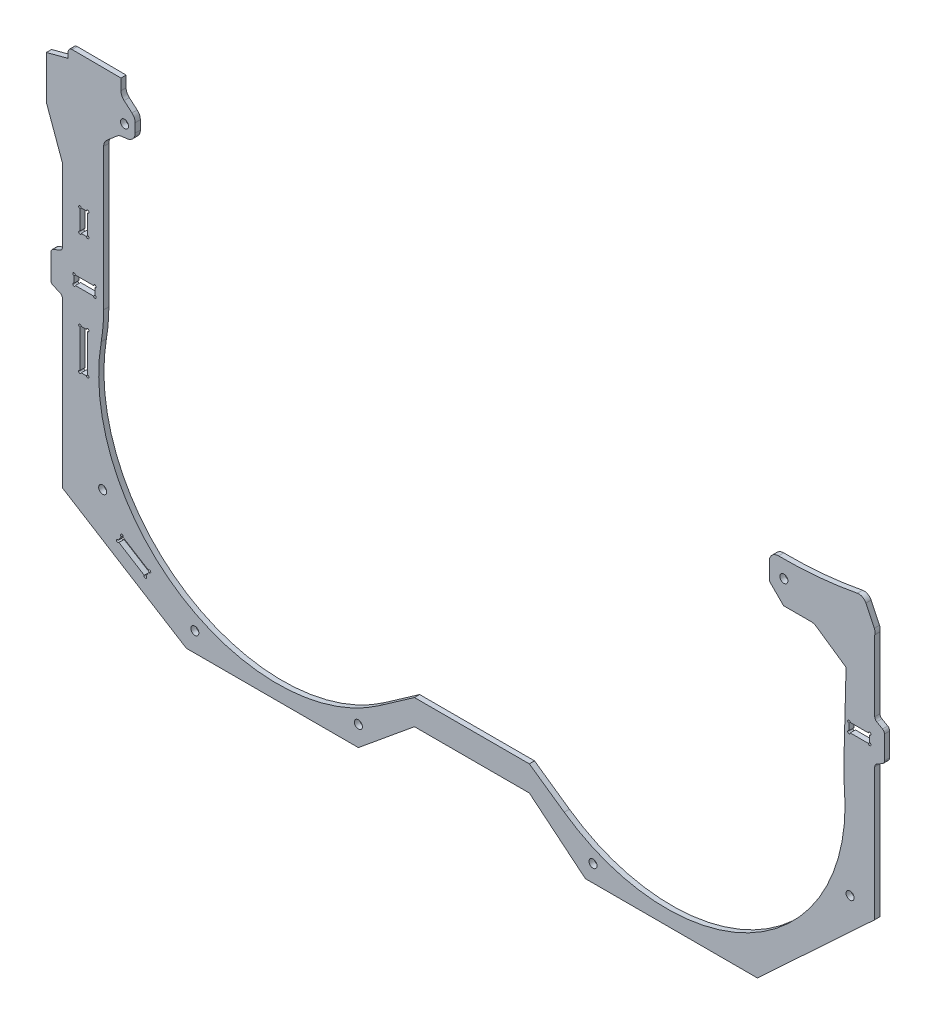
SolidWorks part; units mm, degrees
material "PPS"
ref_plane "前视基准面" through (0, 0, 0) normal (0, 0, 1) x (1, 0, 0)
ref_plane "上视基准面" through (0, 0, 0) normal (0, 1, 0) x (1, 0, 0)
ref_plane "右视基准面" through (0, 0, 0) normal (1, 0, 0) x (0, 0, -1)
sketch "草图1" plane through (0, 0, 0) normal (0, 0, 1) x (1, 0, 0)
  line L0 (-816.4831, 0) -> (39952.7477, 0) construction
  line L1 (0, 10.8762) -> (0, -592.6628) construction
  line L2 (0, 0) -> (206.9686, -284.8678) construction
  line L9 (155.1848, -135.6229) -> (109.9887, -177.6457)
  line L10 (109.9887, -177.6457) -> (43.7257, -177.6457)
  line L60 (-109.9887, -177.6457) -> (-43.7257, -177.6457)
  line L119 (-135.8935, -19.3983) -> (-141.8504, -24.5203)
  line L187 (152.75, -77.5) -> (145.75, -77.5) construction
  line L188 (152.75, -77.5) -> (152.75, -75) construction
  line L189 (145.75, -77.5) -> (145.75, -75) construction
  line L190 (152.75, -75) -> (145.75, -75) construction
  line L191 (-145.75, -75) -> (-152.75, -75) construction
  line L192 (-152.75, -75) -> (-152.75, -77.5) construction
  line L193 (-152.75, -77.5) -> (-145.75, -77.5) construction
  line L194 (-145.75, -77.5) -> (-145.75, -75) construction
  line L195 (145.25, -74.5) -> (153.25, -74.5)
  line L196 (153.25, -74.5) -> (153.25, -78)
  line L197 (153.25, -78) -> (145.25, -78)
  line L198 (145.25, -78) -> (145.25, -74.5)
  line L199 (-153.25, -78) -> (-145.25, -78)
  line L200 (-153.25, -74.5) -> (-153.25, -78)
  line L201 (-145.25, -74.5) -> (-153.25, -74.5)
  line L202 (-145.25, -78) -> (-145.25, -74.5)
  line L204 (-135.1929, 0) -> (-155.5041, 0.108)
  line L205 (-155.5041, 3.8169) -> (-155.5041, -3.6009) construction
  line L206 (-155.5041, 0.108) -> (-155.5041, -3.6009)
  line L207 (-155.5041, -3.6009) -> (-163.9299, -5.8429)
  line L208 (-155.5041, -3.6009) -> (-170.0041, -7.4592) construction
  line L209 (-163.9299, -5.8429) -> (-163.9299, -22.4613)
  line L210 (-163.9299, -22.4613) -> (-157.7253, -39.5836)
  line L211 (-157.7253, -39.5836) -> (-157.7253, -148.0115)
  line L212 (-157.7253, -148.0115) -> (-109.9887, -177.6457)
  line L215 (114.5778, -32.685) -> (114.5778, -42.9165)
  line L216 (120.0778, -48.4165) -> (131.782, -48.4165)
  line L217 (131.782, -48.4165) -> (144.1391, -56.9362)
  line L219 (151.7709, -31.6811) -> (155.0114, -38.4796)
  line L220 (155.1848, -40.6053) -> (155.1848, -135.6229)
  line L221 (120.1823, -39.335) -> (149.4323, -39.335) construction
  line L222 (91.0014, -48.4165) -> (142.5788, -48.4165) construction
  line L223 (75, -103.2286) -> (164.6276, -103.2286) construction
  line L224 (75, -103.2286) -> (35.5666, -159.5453) construction
  line L226 (35.5666, -159.5453) -> (22.126, -150.1341)
  line L227 (22.126, -150.1341) -> (-22.126, -150.1341)
  line L228 (22.126, -159.8702) -> (-22.126, -159.8702)
  line L229 (22.126, -159.8702) -> (43.7257, -177.6457)
  line L230 (-35.5666, -159.5453) -> (-22.126, -150.1341)
  line L231 (-22.126, -159.8702) -> (-43.7257, -177.6457)
  line L233 (114.5778, -42.9165) -> (120.0778, -48.4165)
  line L234 (75, -103.2286) -> (143.1618, -94.255) construction
  line L235 (144.1391, -56.9362) -> (143.1618, -94.255)
  line L236 (143.1618, -94.255) -> (143.1618, -60.7022) construction
  line L238 (-141.8504, -87.1793) -> (-75, -103.2286) construction
  line L239 (-75, -103.2286) -> (-143.75, -103.2286) construction
  line L240 (-141.8504, -24.5203) -> (-141.8504, -87.1793)
  line L241 (-135.1929, 0) -> (-135.1929, -5.85)
  line L242 (-135.1929, -5.85) -> (-129.7197, -10.5767)
  line L243 (-129.7197, -10.5767) -> (-129.7197, -18.7984)
  line L244 (-129.7197, -18.7984) -> (-135.8935, -19.3983)
  circle A76 centre (75, -103.2286) radius 68.75 construction
  circle A78 centre (-133.8062, -14.6009) radius 1.55
  arc A79 (155.0114, -38.4796) -> (155.1848, -40.6053) centre (152.3033, -39.7704) cw
  circle A80 centre (-75, -103.2286) radius 68.75 construction
  arc A81 (148.5011, -30.0249) -> (151.7709, -31.6811) centre (149.0628, -32.9719) cw
  arc A82 (153.902, -42.309) -> (155.0114, -38.4796) centre (152.3033, -39.7704) ccw construction
  arc A83 (148.5011, -30.0249) -> (114.5778, -32.685) centre (119.5082, 122.0773) cw
  arc A84 (97.7907, -31.2329) -> (148.5011, -30.0249) centre (119.5082, 122.0773) ccw construction
  circle A85 centre (149.4323, -39.335) radius 1.55 construction
  circle A86 centre (120.1823, -39.335) radius 1.55
  arc A87 (35.5666, -159.5453) -> (143.75, -103.2286) centre (75, -103.2286) ccw
  arc A88 (-35.5666, -159.5453) -> (-143.75, -103.2286) centre (-75, -103.2286) cw
  arc A89 (143.1618, -94.255) -> (143.75, -103.2286) centre (75, -103.2286) cw
  arc A91 (-143.75, -103.2286) -> (-141.8504, -87.1793) centre (-75, -103.2286) cw
  point P10 (149.25, -75)
  point P29 (0, -150.1341)
  point P32 (110.8616, -177.1038)
  point P38 (153.25, -76.25)
  point P92 (0, -159.8702)
  dimension "D1" = 36
  dimension "D2" = 75
  dimension "D3" = 137.5
  dimension "D6" = 75
  dimension "D7" = 149.25
  dimension "D15" = 125
  dimension "D14" = 3.1
  dimension "D4" = 2.5
  dimension "D5" = 7
  dimension "D8" = 7
  dimension "D9" = 0.5
  dimension "D10" = 0.5
  dimension "D11" = 0.5
  dimension "D12" = 0.5
  dimension "D13" = 29.25
  dimension "D16" = 7.5
  dimension "D17" = 1.5
  dimension "D18" = 13.5
extrude "凸台-拉伸1" add sketch "草图1" along normal blind 2
sketch "草图2" plane through (0, 0, 0) normal (0, 0, 1) x (1, 0, 0)
  line L0 (155.1848, -68.75) -> (158.9348, -70.9151)
  line L1 (155.1848, -135.6229) -> (155.1848, -40.6053) construction
  line L2 (158.9348, -70.9151) -> (158.9348, -81.5849)
  line L3 (158.9348, -81.5849) -> (155.1848, -83.75)
  line L4 (155.1848, -83.75) -> (155.1848, -68.75)
  line L5 (153.25, -76.25) -> (184.2947, -76.25) construction
  line L6 (153.25, -78) -> (153.25, -74.5) construction
  line L7 (-153.25, -76.25) -> (-171.2105, -76.25) construction
  line L8 (-153.25, -74.5) -> (-153.25, -78) construction
  line L9 (-157.7253, -68.75) -> (-157.7253, -83.75)
  line L10 (-157.7253, -39.5836) -> (-157.7253, -148.0115) construction
  line L11 (-157.7253, -83.75) -> (-162.2253, -81.886)
  line L12 (-162.2253, -81.886) -> (-162.2253, -70.614)
  line L13 (-162.2253, -70.614) -> (-157.7253, -68.75)
  dimension "D1" = 3.75
  dimension "D2" = 7.5
  dimension "D3" = 60
  dimension "D4" = 67.5
  dimension "D5" = 4.5
extrude "凸台-拉伸2" add sketch "草图2" against normal up to surface from surface up to face at (-132.2562, -14.6009, 0) starting at face at (149.25, -76.25, 2)
fillet "圆角1" radius 66.25 2 edges at (-141.8504, -87.1793, 1) (143.1618, -94.255, 1)
fillet "圆角4" radius 1.5 9 edges at (155.1848, -68.75, 1) (158.9348, -70.9151, 1) (155.1848, -83.75, 1) (158.9348, -81.5849, 1) (-155.5041, 0.108, 1) (-157.7253, -68.75, 1) (-162.2253, -70.614, 1) (-162.2253, -81.886, 1) (-157.7253, -83.75, 1)
sketch "板状设备接口" plane through (0, 0, 2) normal (0, 0, 1) x (1, 0, 0)
  line L0 (-151, -90.5) -> (-148, -90.5)
  line L1 (-148, -90.5) -> (-148, -106)
  line L2 (-148, -106) -> (-151, -106)
  line L3 (-151, -106) -> (-151, -90.5)
  line L4 (-148, -77.5) -> (-148, -75) construction
  line L5 (-151, -75) -> (-151, -77.5) construction
  line L6 (-151, -51) -> (-148, -51)
  line L7 (-148, -51) -> (-148, -59.5)
  line L8 (-148, -59.5) -> (-151, -59.5)
  line L9 (-151, -59.5) -> (-151, -51)
  line L10 (-145.25, -74.5) -> (-153.25, -74.5) construction
  line L11 (-153.25, -78) -> (-145.25, -78) construction
  line L12 (-134.8158, -152.523) -> (-124.1957, -159.1157)
  line L13 (-124.1957, -159.1157) -> (-125.778, -161.6645)
  line L14 (-125.778, -161.6645) -> (-136.398, -155.0718)
  line L15 (-136.398, -155.0718) -> (-134.8158, -152.523)
  line L21 (-157.7253, -148.0115) -> (-109.9887, -177.6457) construction
  line L22 (-131.088, -158.3682) -> (-133.857, -162.8286) construction
  dimension "D1" = 15
  dimension "D2" = 8.5
  dimension "D3" = 12.5
  dimension "D4" = 15.5
  dimension "D5" = 5.25
  dimension "D6" = 12.5
  dimension "D7" = 3
extrude "设备接口" cut sketch "板状设备接口" against normal through all
sketch "草图4" plane through (0, 0, 0) normal (0, 0, 1) x (1, 0, 0)
  line L0 (-157.7253, -84.7523) -> (-157.7253, -148.0115) construction
  line L1 (-109.9887, -177.6457) -> (-43.7257, -177.6457) construction
  line L2 (155.1848, -135.6229) -> (155.1848, -84.616) construction
  line L3 (-43.7257, -169.8957) -> (-43.7257, -177.6457) construction
  line L4 (43.7257, -177.6457) -> (109.9887, -177.6457) construction
  circle A0 centre (-142.2253, -140.8215) radius 1.55
  circle A1 centre (-43.7257, -169.8957) radius 1.55
  circle A2 centre (-106.713, -170.1457) radius 1.55
  circle A3 centre (46.656, -171.1457) radius 1.55
  circle A4 centre (145.6848, -132.301) radius 1.55
  dimension "D5" = 3.1
  dimension "D1" = 15.5
  dimension "D2" = 7.5
  dimension "D3" = 7.75
  dimension "D4" = 9.5
  dimension "D6" = 6.5
extrude "切除-拉伸3" cut sketch "草图4" along normal through all
fillet "圆角5" radius 3.5 7 edges at (131.782, -48.4165, 1) (114.5778, -32.685, 1) (-141.8504, -24.5203, 1) (-129.7197, -10.5767, 1) (-135.1929, -5.85, 1) (-135.8935, -19.3983, 1) (-129.7197, -18.7984, 1)
sketch "过切除" plane through (0, 0, 0) normal (0, 0, 1) x (1, 0, 0)
  circle A0 centre (-151, -51) radius 0.5
  circle A1 centre (-148, -51) radius 0.5
  circle A2 centre (-151, -59.5) radius 0.5
  circle A3 centre (-148, -59.5) radius 0.5
  circle A4 centre (-153.25, -74.5) radius 0.5
  circle A5 centre (-145.25, -74.5) radius 0.5
  circle A6 centre (-145.25, -78) radius 0.5
  circle A7 centre (-153.25, -78) radius 0.5
  circle A8 centre (-151, -90.5) radius 0.5
  circle A9 centre (-148, -90.5) radius 0.5
  circle A10 centre (-151, -106) radius 0.5
  circle A11 centre (-148, -106) radius 0.5
  circle A12 centre (-134.8158, -152.523) radius 0.5
  circle A13 centre (-136.398, -155.0718) radius 0.5
  circle A14 centre (-124.1957, -159.1157) radius 0.5
  circle A15 centre (-125.778, -161.6645) radius 0.5
  circle A16 centre (145.25, -74.5) radius 0.5
  circle A17 centre (153.25, -74.5) radius 0.5
  circle A18 centre (153.25, -78) radius 0.5
  circle A19 centre (145.25, -78) radius 0.5
  dimension "D1" = 1
extrude "这个是因为刀的限制不能切直角" cut sketch "过切除" along normal through all
